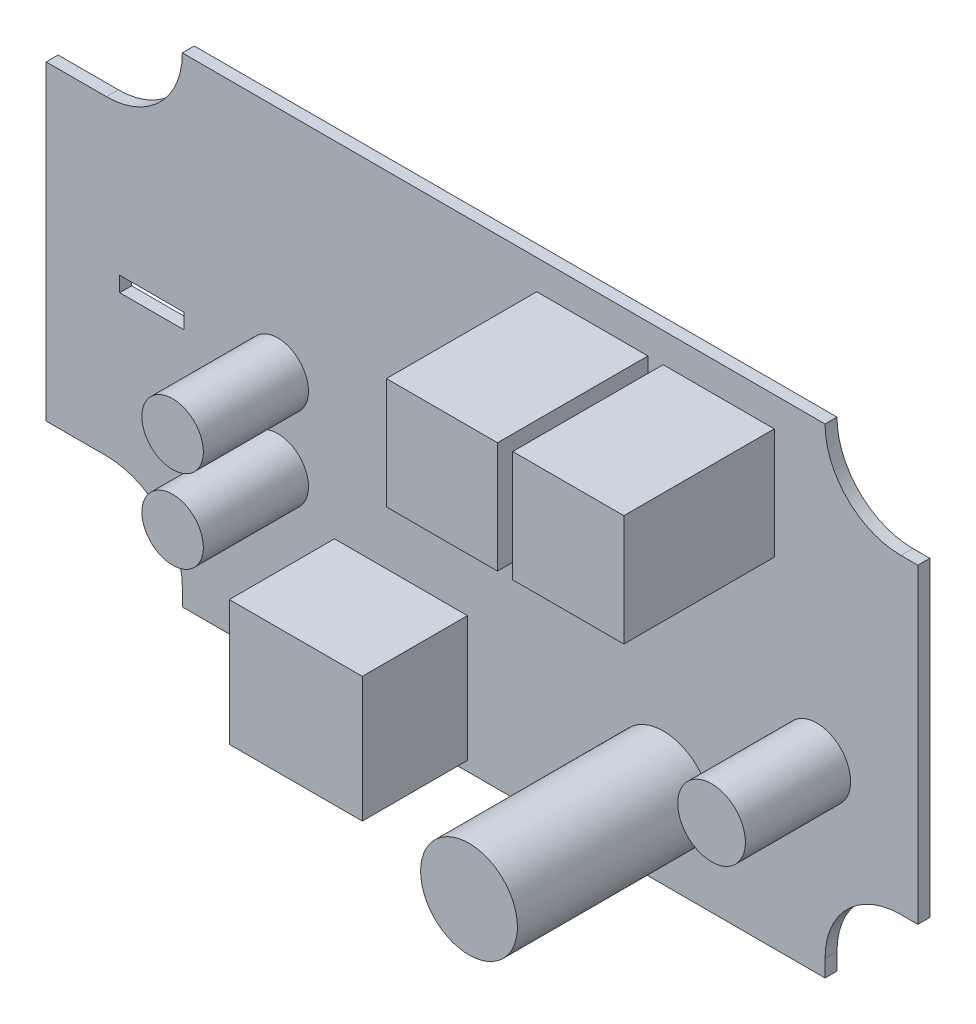
SolidWorks part; units mm, degrees
ref_plane "Front Plane" through (0, 0, 0) normal (0, 0, 1) x (1, 0, 0)
ref_plane "Top Plane" through (0, 0, 0) normal (0, 1, 0) x (1, 0, 0)
ref_plane "Right Plane" through (0, 0, 0) normal (1, 0, 0) x (0, 0, -1)
sketch "Sketch1" plane through (0, 0, 0) normal (0, 0, 1) x (1, 0, 0)
  line L0 (-42.3541, 30.2967) -> (-52.3541, 30.2967) construction
  line L1 (42.3541, -30.7033) -> (42.3541, -32.9433)
  line L2 (-52.3541, -20.7033) -> (-60.3013, -20.7033)
  line L3 (-42.3541, 30.2967) -> (42.3541, 30.2967)
  line L4 (52.3541, -20.7033) -> (54.5933, -20.7033)
  line L5 (-52.3541, 30.2967) -> (-52.3541, 20.2967) construction
  line L6 (-52.3541, -20.7033) -> (-52.3541, -30.7033) construction
  line L7 (-52.3541, -30.7033) -> (-42.3541, -30.7033) construction
  line L8 (42.3541, -30.7033) -> (52.3541, -30.7033) construction
  line L9 (52.3541, -30.7033) -> (52.3541, -20.7033) construction
  line L10 (52.3541, 20.2967) -> (52.3541, 30.2967) construction
  line L11 (52.3541, 30.2967) -> (42.3541, 30.2967) construction
  line L12 (54.5933, -20.7033) -> (54.5933, 20.2967)
  line L13 (-60.3013, -20.7033) -> (-60.3013, 20.2967)
  line L14 (-60.3013, 20.2967) -> (-52.3541, 20.2967)
  line L15 (54.5933, 20.2967) -> (52.3541, 20.2967)
  line L16 (42.3541, -32.9433) -> (-42.3541, -32.9433)
  line L17 (-42.3541, -32.9433) -> (-42.3541, -30.7033)
  line L18 (-50.6088, -0.2033) -> (-60.3013, -0.2033) construction
  line L19 (-42.1088, -1.2033) -> (-50.6088, -1.2033)
  line L20 (-42.1088, -1.2033) -> (-42.1088, 0.7967)
  line L21 (0, -32.9433) -> (0, 0) construction
  line L22 (-42.1088, 0.7967) -> (-50.6088, 0.7967)
  line L23 (-50.6088, -1.2033) -> (-50.6088, 0.7967)
  arc A0 (-42.3541, 30.2967) -> (-52.3541, 20.2967) centre (-52.3541, 30.2967) cw
  arc A2 (-52.3541, -20.7033) -> (-42.3541, -30.7033) centre (-52.3541, -30.7033) cw
  arc A4 (42.3541, 30.2967) -> (52.3541, 20.2967) centre (52.3541, 30.2967) ccw
  arc A5 (52.3541, -20.7033) -> (42.3541, -30.7033) centre (52.3541, -30.7033) ccw
  dimension "D1" = 41
  dimension "D2" = 2
  dimension "D3" = 10
  dimension "D4" = 8.5
  dimension "D6" = 2.24
  dimension "D8" = 2.2392
extrude "Boss-Extrude1" add sketch "Sketch1" along normal blind 1.5748
sketch "Sketch2" plane through (0, 0, 1.5748) normal (0, 0, 1) x (1, 0, 0)
  line L1 (4.3619, 26.3914) -> (19.0119, 26.3914)
  line L2 (4.3619, 26.3914) -> (4.3619, 11.7414)
  line L3 (4.3619, 11.7414) -> (19.0119, 11.7414)
  line L4 (19.0119, 26.3914) -> (19.0119, 11.7414)
  line L5 (21.0119, 26.3914) -> (35.6619, 26.3914)
  line L6 (21.0119, 26.3914) -> (21.0119, 11.7414)
  line L7 (21.0119, 11.7414) -> (35.6619, 11.7414)
  line L8 (35.6619, 26.3914) -> (35.6619, 11.7414)
  dimension "D1" = 2
  dimension "D2" = 14.65
extrude "Boss-Extrude2" add sketch "Sketch2" along normal blind 19.82
sketch "Sketch3" plane through (0, 0, 1.5748) normal (0, 0, 1) x (1, 0, 0)
  circle A0 centre (21.0509, -21.7791) radius 6.38
  dimension "D1" = 12.76
extrude "Boss-Extrude3" add sketch "Sketch3" along normal blind 25.62
sketch "Sketch4" plane through (0, 0, 1.5748) normal (0, 0, 1) x (1, 0, 0)
  line L1 (-22.3027, -15.1438) -> (-4.7739, -15.1438)
  line L2 (-22.3027, -15.1438) -> (-22.3027, -31.671)
  line L3 (-22.3027, -31.671) -> (-4.7739, -31.671)
  line L4 (-4.7739, -15.1438) -> (-4.7739, -31.671)
  circle A0 centre (-29.7754, 0) radius 4.05
  circle A1 centre (-29.7754, -10.91) radius 4.05
  circle A2 centre (41.2613, -8.8411) radius 4.4585
  dimension "D1" = 8.1
  dimension "D2" = 16.5272
  dimension "D4" = 8.9169
  dimension "D3" = 17.5288
extrude "Boss-Extrude4" add sketch "Sketch4" along normal blind 13.86
